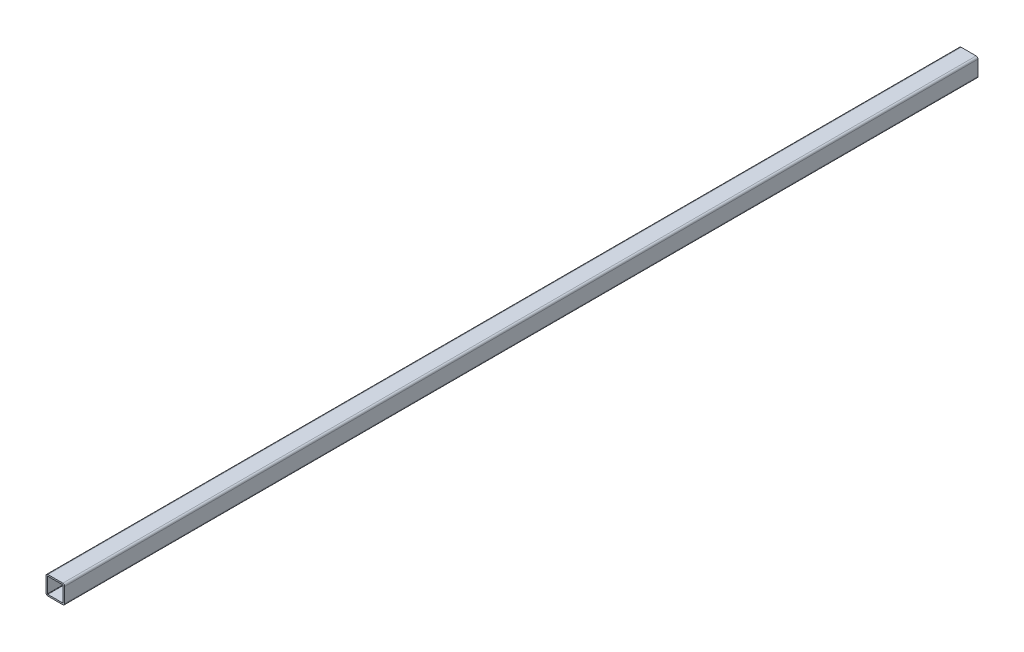
SolidWorks part; units mm, degrees
material "6063-T4"
ref_plane "Front Plane" through (0, 0, 0) normal (0, 0, 1) x (1, 0, 0)
ref_plane "Top Plane" through (0, 0, 0) normal (0, 1, 0) x (1, 0, 0)
ref_plane "Right Plane" through (0, 0, 0) normal (1, 0, 0) x (0, 0, -1)
sketch "Sketch1" plane through (0, 0, 0) normal (0, 0, 1) x (1, 0, 0)
  line L1 (10, -12.5) -> (-10, -12.5)
  line L2 (12.5, -10) -> (12.5, 10)
  line L3 (10, 12.5) -> (-10, 12.5)
  line L4 (-12.5, -10) -> (-12.5, 10)
  line L5 (12.5, -12.5) -> (-12.5, 12.5) construction
  line L6 (12.5, 12.5) -> (-12.5, -12.5) construction
  arc A0 (-10, 12.5) -> (-12.5, 10) centre (-10, 10) ccw
  arc A1 (12.5, 10) -> (10, 12.5) centre (10, 10) ccw
  arc A2 (10, -12.5) -> (12.5, -10) centre (10, -10) ccw
  arc A3 (-10, -12.5) -> (-12.5, -10) centre (-10, -10) cw
  point P0 (0, 0)
  dimension "D2" = 2.5
  dimension "D1" = 25
extrude "Extrude-Thin1" add sketch "Sketch1" along normal mid plane 1219.2 thin thin type one direction reverse wall 2
equation "\"D2@Sketch1\" = \"D5@Extrude-Thin1\" * 1.25"
